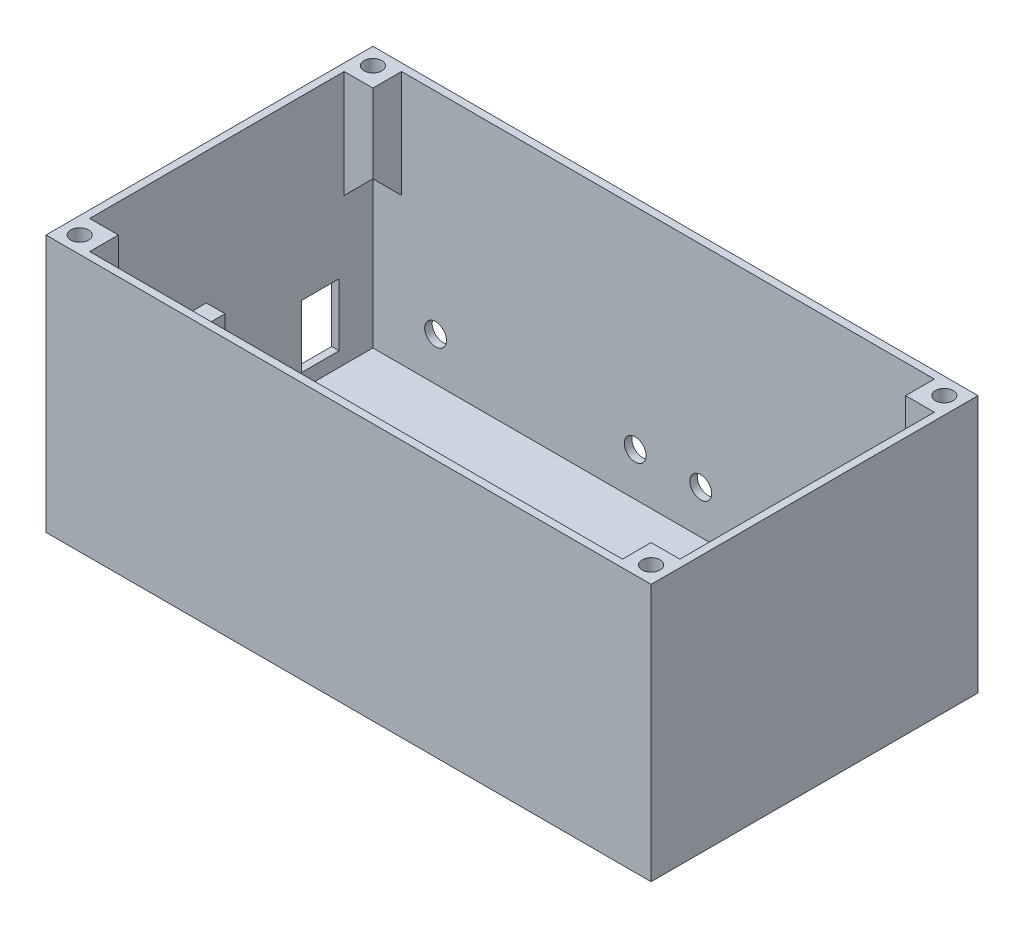
SolidWorks part; units mm, degrees
ref_plane "Front" through (0, 0, 0) normal (0, 0, 1) x (1, 0, 0)
ref_plane "Top" through (0, 0, 0) normal (0, 1, 0) x (1, 0, 0)
ref_plane "Right" through (0, 0, 0) normal (1, 0, 0) x (0, 0, -1)
sketch "Skizze1" plane through (0, 0, 0) normal (0, 0, 1) x (1, 0, 0)
  line L0 (91, 4.0307) -> (91, 39.2807) construction
  line L1 (0, 0) -> (97, 0)
  line L2 (0, 0) -> (0, 41.2807)
  line L3 (0, 41.2807) -> (97, 41.2807)
  line L4 (97, 0) -> (97, 41.2807)
  dimension "D1" = 6
extrude "Aufsatz-Linear austragen1" add sketch "Skizze1" along normal blind 1.2
sketch "Skizze2" plane through (0, 0, 1.2) normal (0, 0, 1) x (1, 0, 0)
  line L0 (0, 0) -> (0, 41.2807)
  line L1 (0, 41.2807) -> (1.2, 41.2807)
  line L2 (97, 41.2807) -> (0, 41.2807) construction
  line L3 (1.2, 41.2807) -> (1.2, 0.6)
  line L4 (1.2, 0.6) -> (95.8, 0.6)
  line L5 (48.5, 0) -> (48.5, -11.9593)
  line L6 (0, 0) -> (97, 0) construction
  line L7 (0, 0) -> (97, 0)
  line L8 (97, 0) -> (97, 41.2807)
  line L9 (97, 41.2807) -> (95.8, 41.2807)
  line L10 (95.8, 41.2807) -> (95.8, 0.6)
  point P16 (48.5, 0.6)
  line M7 (0, 41.2807) -> (0, 0)
  line M8 (0, 0) -> (97, 0)
  line M9 (97, 0) -> (97, 41.2807)
  line M10 (97, 41.2807) -> (0, 41.2807)
  dimension "D1" = 1.2
  dimension "D2" = 0.6
extrude "Aufsatz-Linear austragen2" add sketch "Skizze2" along normal blind 50 contours L10 L4 L3 M10 M7 M8 M9 region at (1.0542, 20.6404, 1.2)
sketch "Skizze3" plane through (1.2, 0, 0) normal (1, 0, 0) x (0, 0, -1)
  line L0 (-47.3, 17.2) -> (-30.9, 17.2)
  line L1 (-30.9, 17.2) -> (-30.9, 2.4)
  line L2 (-30.9, 2.4) -> (-47.3, 2.4)
  line L3 (-47.3, 2.4) -> (-47.3, 17.2)
  line L4 (-51.2, 20.2) -> (-27.9, 20.2)
  line L5 (-27.9, 20.2) -> (-27.9, 0.6)
  line L7 (-51.2, 0.6) -> (-1.2, 0.6) construction
  line L8 (-51.2, 41.2807) -> (-51.2, 0.6) construction
  line L9 (-51.2, 20.2) -> (-51.2, 0.6)
  line L10 (-51.2, 0.6) -> (-27.9, 0.6)
  dimension "D1" = 16.4
  dimension "D2" = 14.8
  dimension "D3" = 3
  dimension "D4" = 3
  dimension "D5" = 1.8
  dimension "D6" = 3.9
extrude "Aufsatz-Linear austragen3" add sketch "Skizze3" along normal blind 3
extrude "Schnitt-Linear austragen1" cut sketch "Skizze3<2>" against normal through all contours L3 L2 L1 L0 region at (1.2, 9.8, 39.1)
sketch "Skizze3<2>" plane through (1.2, 0, 0) normal (1, 0, 0) x (0, 0, -1) same geometry as "Skizze3"
sketch "Skizze5" plane through (0, 0, 51.2) normal (0, 0, 1) x (1, 0, 0)
  line L1 (0, 0) -> (97, 0)
  line L2 (0, 0) -> (0, 41.2807)
  line L3 (0, 41.2807) -> (97, 41.2807)
  line L4 (97, 0) -> (97, 41.2807)
extrude "Aufsatz-Linear austragen4" add sketch "Skizze5" along normal blind 1.2
sketch "Skizze6" plane through (0, 41.2807, 0) normal (0, 1, 0) x (1, 0, 0)
  line L1 (0, -52.4) -> (34.6832, -52.4)
  line L2 (0, -52.4) -> (0, -25.3437)
  line L3 (0, -25.3437) -> (34.6832, -25.3437)
  line L4 (34.6832, -52.4) -> (34.6832, -25.3437)
  line L5 (-5.6828, -56.2564) -> (100.3372, -56.2564)
  line L6 (-5.6828, -56.2564) -> (-5.6828, 8.0741)
  line L7 (-5.6828, 8.0741) -> (100.3372, 8.0741)
  line L8 (100.3372, -56.2564) -> (100.3372, 8.0741)
extrude "Schnitt-Linear austragen2" [suppressed] cut sketch "Skizze6" against normal through all
sketch "Skizze7" plane through (0, 41.2807, 0) normal (0, 1, 0) x (1, 0, 0)
  line L0 (1.2, -1.2) -> (95.8, -1.2) construction
  line L1 (1.2, -27.9) -> (1.2, -1.2) construction
  line L2 (1.2, -5.8) -> (5.8, -5.8)
  line L3 (1.2, -51.2) -> (1.2, -1.2) construction
  line L4 (5.8, -5.8) -> (5.8, -1.2)
  line L5 (5.8, -1.2) -> (1.2, -1.2)
  line L6 (1.2, -1.2) -> (1.2, -5.8)
  line L7 (0, -52.4) -> (0, 0) construction
  line L8 (48.5, -1.2) -> (48.5, -37.1264) construction
  line L9 (1.2, -26.2) -> (37.9738, -26.2) construction
  line L10 (95.8, -1.2) -> (95.8, -5.8)
  line L11 (91.2, -1.2) -> (95.8, -1.2)
  line L12 (91.2, -5.8) -> (91.2, -1.2)
  line L13 (95.8, -5.8) -> (91.2, -5.8)
  line L14 (95.8, -46.6) -> (91.2, -46.6)
  line L15 (91.2, -46.6) -> (91.2, -51.2)
  line L16 (91.2, -51.2) -> (95.8, -51.2)
  line L17 (95.8, -51.2) -> (95.8, -46.6)
  line L18 (1.2, -51.2) -> (1.2, -46.6)
  line L19 (5.8, -51.2) -> (1.2, -51.2)
  line L20 (5.8, -46.6) -> (5.8, -51.2)
  line L21 (1.2, -46.6) -> (5.8, -46.6)
  circle A0 centre (2.7, -2.7) radius 1.425
  circle A1 centre (94.3, -2.7) radius 1.425
  circle A2 centre (94.3, -49.7) radius 1.425
  circle A3 centre (2.7, -49.7) radius 1.425
  dimension "D1" = 2.85
  dimension "D2" = 1.5
  dimension "D3" = 1.5
  dimension "D5" = 5.8
extrude "Aufsatz-Linear austragen5" add sketch "Skizze7" against normal blind 12
sketch "Skizze8" plane through (0, 0, 1.2) normal (0, 0, 1) x (1, 0, 0)
  circle A0 centre (11.25, 7.5307) radius 1.75
  circle A1 centre (43.25, 7.5307) radius 1.75
  circle A2 centre (53.75, 7.5307) radius 1.75
  circle A3 centre (85.75, 7.5307) radius 1.75
  dimension "D1" = 3.5
extrude "Schnitt-Linear austragen3" cut sketch "Skizze8" against normal blind 12
sketch "Skizze9" plane through (0, 0, 0) normal (-1, 0, 0) x (0, 0, 1)
  line L1 (6.6051, 2.9103) -> (12.6051, 2.9103)
  line L2 (6.6051, 2.9103) -> (6.6051, 12.9103)
  line L3 (6.6051, 12.9103) -> (12.6051, 12.9103)
  line L4 (12.6051, 2.9103) -> (12.6051, 12.9103)
  dimension "D1" = 10
  dimension "D2" = 6
extrude "Schnitt-Linear austragen4" cut sketch "Skizze9" against normal blind 12
sketch "Skizze10" plane through (0, 29.2807, 0) normal (0, -1, 0) x (1, 0, 0)
  line L1 (5.8, 46.6) -> (1.2, 46.6)
  line L2 (5.8, 46.6) -> (5.8, 51.2)
  line L3 (5.8, 51.2) -> (1.2, 51.2)
  line L4 (1.2, 46.6) -> (1.2, 51.2)
  line L5 (5.8, 5.8) -> (1.2, 5.8)
  line L6 (5.8, 5.8) -> (5.8, 1.2)
  line L7 (5.8, 1.2) -> (1.2, 1.2)
  line L8 (1.2, 5.8) -> (1.2, 1.2)
  line L9 (91.2, 46.6) -> (95.8, 46.6)
  line L10 (91.2, 46.6) -> (91.2, 51.2)
  line L11 (91.2, 51.2) -> (95.8, 51.2)
  line L12 (95.8, 46.6) -> (95.8, 51.2)
  line L13 (91.2, 5.8) -> (95.8, 5.8)
  line L14 (91.2, 5.8) -> (91.2, 1.2)
  line L15 (91.2, 1.2) -> (95.8, 1.2)
  line L16 (95.8, 5.8) -> (95.8, 1.2)
extrude "Aufsatz-Linear austragen6" add sketch "Skizze10" along normal blind 0.6
chamfer "Fase1" distance 4.6 angle 45 8 edges at (1.2, 28.6807, 3.5) (3.5, 28.6807, 1.2) (93.5, 28.6807, 1.2) (95.8, 28.6807, 3.5) (95.8, 28.6807, 48.9) (93.5, 28.6807, 51.2) (1.2, 28.6807, 48.9) (3.5, 28.6807, 51.2)
